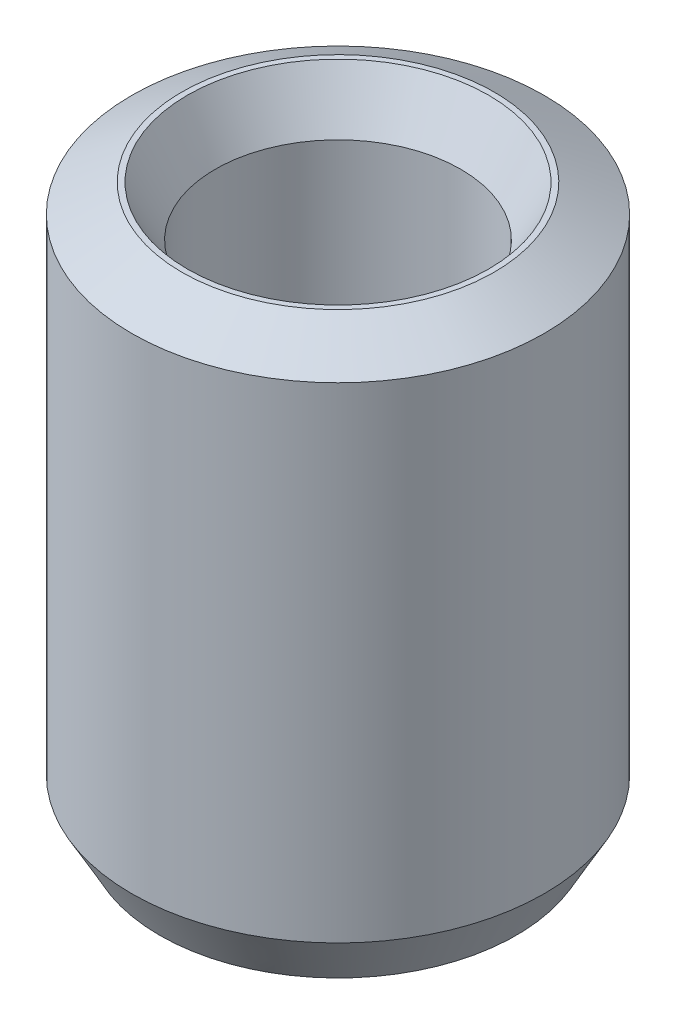
SolidWorks part; units mm, degrees
ref_plane "Front Plane" through (0, 0, 0) normal (0, 0, 1) x (1, 0, 0)
ref_plane "Top Plane" through (0, 0, 0) normal (0, 1, 0) x (1, 0, 0)
ref_plane "Right Plane" through (0, 0, 0) normal (1, 0, 0) x (0, 0, -1)
sketch "Sketch1" plane through (0, 0, 0) normal (0, 1, 0) x (1, 0, 0)
  circle A0 centre (0, 0) radius 12.5
  dimension "SLEEVE_OD" = 25
extrude "Boss-Extrude1" add sketch "Sketch1" along normal blind 34.136
sketch "Sketch2" plane through (0, 0, 0) normal (0, 1, 0) x (1, 0, 0)
  circle A0 centre (0, 0) radius 7.4344
  dimension "BORE_D" = 14.8687
extrude "Cut-Extrude1" cut sketch "Sketch2" along normal through all
chamfer "Chamfer1" distance 1.6942 angle 60.835 4 edges at (0, 34.136, 7.4344) (0, 0, 7.4344) (0, 0, 12.5) (0, 34.136, 12.5) first distance on face at (0, 34.136, 7.4344) first distance on face at (0, 0, 7.4344) first distance on face at (0, 34.136, 12.5)
